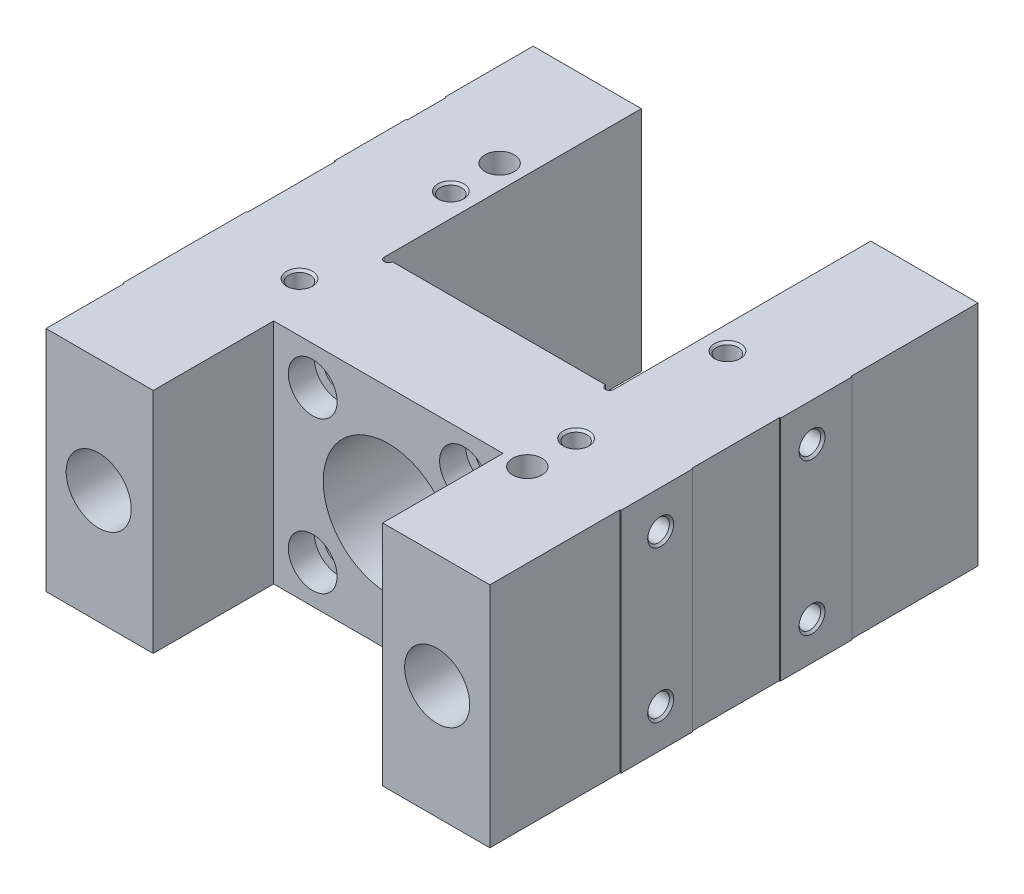
SolidWorks part; units mm, degrees
ref_plane "Front Plane" through (0, 0, 0) normal (0, 0, 1) x (1, 0, 0)
ref_plane "Top Plane" through (0, 0, 0) normal (0, 1, 0) x (1, 0, 0)
ref_plane "Right Plane" through (0, 0, 0) normal (1, 0, 0) x (0, 0, -1)
sketch "Sketch1" plane through (0, 0, 0) normal (0, 1, 0) x (1, 0, 0)
  line L0 (-68.5, -71) -> (-35.25, -71)
  line L1 (-35.25, -71) -> (-35.25, -34)
  line L2 (-35.25, -34) -> (35.25, -34)
  line L3 (35.25, -34) -> (35.25, -71)
  line L4 (35.25, -71) -> (68.5, -71)
  line L5 (68.5, -71) -> (68.5, 79)
  line L6 (68.5, 79) -> (35.25, 79)
  line L7 (35.25, 79) -> (35.25, 0)
  line L8 (32.75, 0) -> (-32.75, 0)
  line L9 (-35.25, 0) -> (-35.25, 79)
  line L10 (-35.25, 79) -> (-68.5, 79)
  line L11 (-68.5, 79) -> (-68.5, -71)
  arc A0 (35.25, 0) -> (32.75, 0) centre (34, 0) cw
  arc A1 (-32.75, 0) -> (-35.25, 0) centre (-34, 0) cw
extrude "Boss-Extrude1" add sketch "Sketch1" against normal blind 35 and the other way blind 35
sketch "Sketch2" plane through (0, 0, 0) normal (1, 0, 0) x (0, 0, -1)
  line L0 (-35, 0) -> (-35, 20)
  line L1 (-35, 20) -> (1, 20)
  line L2 (1, 20) -> (1, 0)
  line L3 (1, 0) -> (-35, 0)
  line L4 (1, 0) -> (-35, 0) construction
revolve "Cut-Revolve1" cut sketch "Sketch2" angle 360 about L4 reverse direction yes
ref_plane "Plane1" through (-23.25, 0, 0) normal (1, 0, 0) x (0, 0, -1)
sketch "Sketch3" plane through (-23.25, 0, 0) normal (1, 0, 0) x (0, 0, -1)
  line L0 (-34, 23.25) -> (-34, 30.75)
  line L1 (-34, 30.75) -> (-26, 30.75)
  line L2 (-26, 30.75) -> (-26, 27.75)
  line L3 (-26, 27.75) -> (0, 27.75)
  line L4 (0, 27.75) -> (0, 23.25)
  line L5 (0, 23.25) -> (-34, 23.25)
  line L6 (0, 23.25) -> (-34, 23.25) construction
revolve "Cut-Revolve2" cut sketch "Sketch3" angle 360 about L6 reverse direction yes
sketch "Sketch4" plane through (-23.25, 0, 0) normal (1, 0, 0) x (0, 0, -1)
  line L0 (-34, -23.25) -> (-34, -15.75)
  line L1 (-34, -15.75) -> (-26, -15.75)
  line L2 (-26, -15.75) -> (-26, -18.75)
  line L3 (-26, -18.75) -> (0, -18.75)
  line L4 (0, -18.75) -> (0, -23.25)
  line L5 (0, -23.25) -> (-34, -23.25)
  line L6 (0, -23.25) -> (-34, -23.25) construction
revolve "Cut-Revolve3" cut sketch "Sketch4" angle 360 about L6 reverse direction yes
ref_plane "Plane2" through (23.25, 0, 0) normal (1, 0, 0) x (0, 0, -1)
sketch "Sketch5" plane through (23.25, 0, 0) normal (1, 0, 0) x (0, 0, -1)
  line L0 (-34, 23.25) -> (-34, 30.75)
  line L1 (-34, 30.75) -> (-26, 30.75)
  line L2 (-26, 30.75) -> (-26, 27.75)
  line L3 (-26, 27.75) -> (0, 27.75)
  line L4 (0, 27.75) -> (0, 23.25)
  line L5 (0, 23.25) -> (-34, 23.25)
  line L6 (0, 23.25) -> (-34, 23.25) construction
revolve "Cut-Revolve4" cut sketch "Sketch5" angle 360 about L6 reverse direction yes
sketch "Sketch6" plane through (23.25, 0, 0) normal (1, 0, 0) x (0, 0, -1)
  line L0 (-34, -23.25) -> (-34, -15.75)
  line L1 (-34, -15.75) -> (-26, -15.75)
  line L2 (-26, -15.75) -> (-26, -18.75)
  line L3 (-26, -18.75) -> (0, -18.75)
  line L4 (0, -18.75) -> (0, -23.25)
  line L5 (0, -23.25) -> (-34, -23.25)
  line L6 (0, -23.25) -> (-34, -23.25) construction
revolve "Cut-Revolve5" cut sketch "Sketch6" angle 360 about L6 reverse direction yes
ref_plane "Plane3" through (0, 0, 18.8) normal (0, 0, 1) x (1, 0, 0)
hole_wizard "Hole1" positions "Sketch8" profile "Sketch7" legacy
sketch "Sketch8" plane through (0, 35, 0) normal (0, 1, 0) x (1, 0, 0)
  point P0 (42.5, -18.8)
sketch "Sketch7" plane through (42.5, 35, 18.8) normal (1, 0, 0) x (0, 0, 1)
  line L0 (0, 0) -> (0, 21.3333)
  line L1 (0, 21.3333) -> (3.3235, 19.4145)
  line L2 (3.3235, 19.4145) -> (3.3235, 0.6765)
  line L3 (3.3235, 0.6765) -> (4, 0)
  line L4 (4, 0) -> (0, 0)
  line L5 (0, -14.3089) -> (0, 102.4216) construction
  line L6 (0, 21.3333) -> (-3.3235, 19.4145) construction
  line L7 (-3.3235, 0.6765) -> (-4, 0) construction
  dimension "Diameter" = 6.647
  dimension "Depth" = 19.4145
  dimension "C-Sink Diameter" = 8
  dimension "C-Sink Angle" = 90
  dimension "Drill Angle" = 120
cosmetic thread "Cosmetic Thread1" parameters "D1"=16, "D2"=8
hole_wizard "Hole2" positions "Sketch10" profile "Sketch9" legacy
sketch "Sketch10" plane through (0, 35, 0) normal (0, 1, 0) x (1, 0, 0)
  point P0 (-42.5, -18.8)
sketch "Sketch9" plane through (-42.5, 35, 18.8) normal (1, 0, 0) x (0, 0, 1)
  line L0 (0, 0) -> (0, 21.3333)
  line L1 (0, 21.3333) -> (3.3235, 19.4145)
  line L2 (3.3235, 19.4145) -> (3.3235, 0.6765)
  line L3 (3.3235, 0.6765) -> (4, 0)
  line L4 (4, 0) -> (0, 0)
  line L5 (0, -14.3089) -> (0, 102.4216) construction
  line L6 (0, 21.3333) -> (-3.3235, 19.4145) construction
  line L7 (-3.3235, 0.6765) -> (-4, 0) construction
  dimension "Diameter" = 6.647
  dimension "Depth" = 19.4145
  dimension "C-Sink Diameter" = 8
  dimension "C-Sink Angle" = 90
  dimension "Drill Angle" = 120
cosmetic thread "Cosmetic Thread2" parameters "D1"=16, "D2"=8
sketch "Sketch11" plane through (0, 0, 18.8) normal (0, 0, 1) x (1, 0, 0)
  line L0 (48.5, 23.25) -> (50.4188, 26.5735)
  line L1 (50.4188, 26.5735) -> (67.8235, 26.5735)
  line L2 (67.8235, 26.5735) -> (68.5, 27.25)
  line L3 (68.5, 27.25) -> (68.5, 23.25)
  line L4 (68.5, 23.25) -> (48.5, 23.25)
  line L5 (68.5, 23.25) -> (48.5, 23.25) construction
revolve "Cut-Revolve6" cut sketch "Sketch11" angle 360 about L5
cosmetic thread "Cosmetic Thread3" parameters "D1"=16, "D2"=8
sketch "Sketch12" plane through (0, 0, 18.8) normal (0, 0, 1) x (1, 0, 0)
  line L0 (48.5, -23.25) -> (50.4188, -19.9265)
  line L1 (50.4188, -19.9265) -> (67.8235, -19.9265)
  line L2 (67.8235, -19.9265) -> (68.5, -19.25)
  line L3 (68.5, -19.25) -> (68.5, -23.25)
  line L4 (68.5, -23.25) -> (48.5, -23.25)
  line L5 (68.5, -23.25) -> (48.5, -23.25) construction
revolve "Cut-Revolve7" cut sketch "Sketch12" angle 360 about L5
cosmetic thread "Cosmetic Thread4" parameters "D1"=16, "D2"=8
sketch "Sketch13" plane through (0, 0, 18.8) normal (0, 0, 1) x (1, 0, 0)
  line L0 (-68.5, 23.25) -> (-68.5, 27.25)
  line L1 (-68.5, 27.25) -> (-67.8235, 26.5735)
  line L2 (-67.8235, 26.5735) -> (-50.4188, 26.5735)
  line L3 (-50.4188, 26.5735) -> (-48.5, 23.25)
  line L4 (-48.5, 23.25) -> (-68.5, 23.25)
  line L5 (-48.5, 23.25) -> (-68.5, 23.25) construction
revolve "Cut-Revolve8" cut sketch "Sketch13" angle 360 about L5
cosmetic thread "Cosmetic Thread5" parameters "D1"=16, "D2"=8
sketch "Sketch14" plane through (0, 0, 18.8) normal (0, 0, 1) x (1, 0, 0)
  line L0 (-68.5, -23.25) -> (-68.5, -19.25)
  line L1 (-68.5, -19.25) -> (-67.8235, -19.9265)
  line L2 (-67.8235, -19.9265) -> (-50.4188, -19.9265)
  line L3 (-50.4188, -19.9265) -> (-48.5, -23.25)
  line L4 (-48.5, -23.25) -> (-68.5, -23.25)
  line L5 (-48.5, -23.25) -> (-68.5, -23.25) construction
revolve "Cut-Revolve9" cut sketch "Sketch14" angle 360 about L5 reverse direction yes
cosmetic thread "Cosmetic Thread6" parameters "D1"=16, "D2"=8
ref_plane "Plane4" through (0, 0, -27.7) normal (0, 0, 1) x (1, 0, 0)
hole_wizard "Hole3" positions "Sketch16" profile "Sketch15" legacy
sketch "Sketch16" plane through (0, 35, 0) normal (0, 1, 0) x (1, 0, 0)
  point P0 (42.5, 27.7)
sketch "Sketch15" plane through (42.5, 35, -27.7) normal (1, 0, 0) x (0, 0, 1)
  line L0 (0, 0) -> (0, 21.3333)
  line L1 (0, 21.3333) -> (3.3235, 19.4145)
  line L2 (3.3235, 19.4145) -> (3.3235, 0.6765)
  line L3 (3.3235, 0.6765) -> (4, 0)
  line L4 (4, 0) -> (0, 0)
  line L5 (0, -14.3089) -> (0, 102.4216) construction
  line L6 (0, 21.3333) -> (-3.3235, 19.4145) construction
  line L7 (-3.3235, 0.6765) -> (-4, 0) construction
  dimension "Diameter" = 6.647
  dimension "Depth" = 19.4145
  dimension "C-Sink Diameter" = 8
  dimension "C-Sink Angle" = 90
  dimension "Drill Angle" = 120
cosmetic thread "Cosmetic Thread7" parameters "D1"=16, "D2"=8
sketch "Sketch17" plane through (0, 0, -27.7) normal (0, 0, 1) x (1, 0, 0)
  line L0 (-42.5, 35) -> (-38.5, 35)
  line L1 (-38.5, 35) -> (-39.1765, 34.3235)
  line L2 (-39.1765, 34.3235) -> (-39.1765, 15.5855)
  line L3 (-39.1765, 15.5855) -> (-42.5, 13.6667)
  line L4 (-42.5, 13.6667) -> (-42.5, 35)
  line L5 (-42.5, 13.6667) -> (-42.5, 35) construction
revolve "Cut-Revolve10" cut sketch "Sketch17" angle 360 about L5
cosmetic thread "Cosmetic Thread8" parameters "D1"=16, "D2"=8
sketch "Sketch18" plane through (0, 0, -27.7) normal (0, 0, 1) x (1, 0, 0)
  line L0 (48.5, 23.25) -> (50.4188, 26.5735)
  line L1 (50.4188, 26.5735) -> (67.8235, 26.5735)
  line L2 (67.8235, 26.5735) -> (68.5, 27.25)
  line L3 (68.5, 27.25) -> (68.5, 23.25)
  line L4 (68.5, 23.25) -> (48.5, 23.25)
  line L5 (68.5, 23.25) -> (48.5, 23.25) construction
revolve "Cut-Revolve11" cut sketch "Sketch18" angle 360 about L5
cosmetic thread "Cosmetic Thread9" parameters "D1"=16, "D2"=8
sketch "Sketch19" plane through (0, 0, -27.7) normal (0, 0, 1) x (1, 0, 0)
  line L0 (48.5, -23.25) -> (50.4188, -19.9265)
  line L1 (50.4188, -19.9265) -> (67.8235, -19.9265)
  line L2 (67.8235, -19.9265) -> (68.5, -19.25)
  line L3 (68.5, -19.25) -> (68.5, -23.25)
  line L4 (68.5, -23.25) -> (48.5, -23.25)
  line L5 (68.5, -23.25) -> (48.5, -23.25) construction
revolve "Cut-Revolve12" cut sketch "Sketch19" angle 360 about L5
cosmetic thread "Cosmetic Thread10" parameters "D1"=16, "D2"=8
sketch "Sketch20" plane through (0, 0, -27.7) normal (0, 0, 1) x (1, 0, 0)
  line L0 (-68.5, 23.25) -> (-68.5, 27.25)
  line L1 (-68.5, 27.25) -> (-67.8235, 26.5735)
  line L2 (-67.8235, 26.5735) -> (-50.4188, 26.5735)
  line L3 (-50.4188, 26.5735) -> (-48.5, 23.25)
  line L4 (-48.5, 23.25) -> (-68.5, 23.25)
  line L5 (-48.5, 23.25) -> (-68.5, 23.25) construction
revolve "Cut-Revolve13" cut sketch "Sketch20" angle 360 about L5
cosmetic thread "Cosmetic Thread11" parameters "D1"=16, "D2"=8
sketch "Sketch21" plane through (0, 0, -27.7) normal (0, 0, 1) x (1, 0, 0)
  line L0 (-68.5, -23.25) -> (-68.5, -19.25)
  line L1 (-68.5, -19.25) -> (-67.8235, -19.9265)
  line L2 (-67.8235, -19.9265) -> (-50.4188, -19.9265)
  line L3 (-50.4188, -19.9265) -> (-48.5, -23.25)
  line L4 (-48.5, -23.25) -> (-68.5, -23.25)
  line L5 (-48.5, -23.25) -> (-68.5, -23.25) construction
revolve "Cut-Revolve14" cut sketch "Sketch21" angle 360 about L5
cosmetic thread "Cosmetic Thread12" parameters "D1"=16, "D2"=8
ref_plane "Plane5" through (0, 0, -63) normal (0, 0, 1) x (1, 0, 0)
sketch "Sketch22" plane through (0, 0, -63) normal (0, 0, 1) x (1, 0, 0)
  line L0 (-68.5, 23.25) -> (-68.5, 27.25)
  line L1 (-68.5, 27.25) -> (-67.8235, 26.5735)
  line L2 (-67.8235, 26.5735) -> (-50.4188, 26.5735)
  line L3 (-50.4188, 26.5735) -> (-48.5, 23.25)
  line L4 (-48.5, 23.25) -> (-68.5, 23.25)
  line L5 (-48.5, 23.25) -> (-68.5, 23.25) construction
revolve "Cut-Revolve15" cut sketch "Sketch22" angle 360 about L5
cosmetic thread "Cosmetic Thread13" parameters "D1"=16, "D2"=8
sketch "Sketch23" plane through (0, 0, -63) normal (0, 0, 1) x (1, 0, 0)
  line L0 (-68.5, -23.25) -> (-68.5, -19.25)
  line L1 (-68.5, -19.25) -> (-67.8235, -19.9265)
  line L2 (-67.8235, -19.9265) -> (-50.4188, -19.9265)
  line L3 (-50.4188, -19.9265) -> (-48.5, -23.25)
  line L4 (-48.5, -23.25) -> (-68.5, -23.25)
  line L5 (-48.5, -23.25) -> (-68.5, -23.25) construction
revolve "Cut-Revolve16" cut sketch "Sketch23" angle 360 about L5
cosmetic thread "Cosmetic Thread14" parameters "D1"=16, "D2"=8
ref_plane "Plane6" through (0, 0, 37) normal (0, 0, 1) x (1, 0, 0)
sketch "Sketch24" plane through (0, 0, 37) normal (0, 0, 1) x (1, 0, 0)
  line L0 (-68.5, 23.25) -> (-68.5, 27.25)
  line L1 (-68.5, 27.25) -> (-67.8235, 26.5735)
  line L2 (-67.8235, 26.5735) -> (-50.4188, 26.5735)
  line L3 (-50.4188, 26.5735) -> (-48.5, 23.25)
  line L4 (-48.5, 23.25) -> (-68.5, 23.25)
  line L5 (-48.5, 23.25) -> (-68.5, 23.25) construction
revolve "Cut-Revolve17" cut sketch "Sketch24" angle 360 about L5
cosmetic thread "Cosmetic Thread15" parameters "D1"=16, "D2"=8
sketch "Sketch25" plane through (0, 0, 37) normal (0, 0, 1) x (1, 0, 0)
  line L0 (-68.5, -23.25) -> (-68.5, -19.25)
  line L1 (-68.5, -19.25) -> (-67.8235, -19.9265)
  line L2 (-67.8235, -19.9265) -> (-50.4188, -19.9265)
  line L3 (-50.4188, -19.9265) -> (-48.5, -23.25)
  line L4 (-48.5, -23.25) -> (-68.5, -23.25)
  line L5 (-48.5, -23.25) -> (-68.5, -23.25) construction
revolve "Cut-Revolve18" cut sketch "Sketch25" angle 360 about L5
cosmetic thread "Cosmetic Thread16" parameters "D1"=16, "D2"=8
ref_plane "Plane7" through (0, 0, -79) normal (0, 0, 1) x (1, 0, 0)
sketch "Sketch26" plane through (0, 0, -79) normal (0, 0, 1) x (1, 0, 0)
  circle A0 centre (52, 0) radius 10
extrude "Cut-Extrude1" cut sketch "Sketch26" along normal blind 150
sketch "Sketch27" plane through (0, 0, -79) normal (0, 0, 1) x (1, 0, 0)
  circle A0 centre (-52, 0) radius 10
extrude "Cut-Extrude2" cut sketch "Sketch27" along normal blind 150
ref_plane "Plane8" through (0, 0, 26) normal (0, 0, 1) x (1, 0, 0)
ref_plane "Plane9" through (0, 0, 0) normal (0, 0, 1) x (1, 0, 0)
sketch "Sketch28" plane through (0, 0, 0) normal (0, 1, 0) x (1, 0, 0)
  line L0 (-88.5, -91) -> (88.5, -91)
  line L1 (88.5, -91) -> (88.5, 99)
  line L2 (88.5, 99) -> (-88.5, 99)
  line L3 (-88.5, 99) -> (-88.5, -91)
  line L4 (-68.5, 18) -> (-68.2, 18)
  line L5 (-68.2, 18) -> (-68.2, -9)
  line L6 (-68.2, -9) -> (-68.5, -9)
  line L7 (-68.5, -9) -> (-68.5, -47)
  line L8 (-68.5, -47) -> (-68.2, -47)
  line L9 (-68.2, -47) -> (-68.2, -71)
  line L10 (-68.2, -71) -> (68.2, -71)
  line L11 (68.2, -71) -> (68.2, -31)
  line L12 (68.2, -31) -> (68.5, -31)
  line L13 (68.5, -31) -> (68.5, -9)
  line L14 (68.5, -9) -> (68.2, -9)
  line L15 (68.2, -9) -> (68.2, 18)
  line L16 (68.2, 18) -> (68.5, 18)
  line L17 (68.5, 18) -> (68.5, 40)
  line L18 (68.5, 40) -> (68.2, 40)
  line L19 (68.2, 40) -> (68.2, 79)
  line L20 (68.2, 79) -> (-68.5, 79)
  line L21 (-68.5, 79) -> (-68.5, 52)
  line L22 (-68.5, 52) -> (-68.2, 52)
  line L23 (-68.2, 52) -> (-68.2, 40)
  line L24 (-68.2, 40) -> (-68.5, 40)
  line L25 (-68.5, 40) -> (-68.5, 18)
extrude "Cut-Extrude3" cut sketch "Sketch28" along normal blind 70 and the other way blind 70
ref_plane "Plane10" through (0, 0, 18.8) normal (0, 0, 1) x (1, 0, 0)
ref_plane "Plane11" through (-68.2, 0, 0) normal (1, 0, 0) x (0, 0, -1)
ref_plane "Plane12" through (0, 35, 0) normal (0, 1, 0) x (1, 0, 0)
ref_plane "DIN912 1 XY" through (0, 0, 26) normal (0, 0, 1) x (1, 0, 0)
ref_plane "DIN912 1 XZ" through (0, 23.25, 0) normal (0, -1, 0) x (-1, 0, 0)
ref_plane "DIN912 1 YZ" through (23.25, 0, 0) normal (1, 0, 0) x (0, 0, -1)
ref_axis "DIN912 1 X" through (-80.9, 23.25, 26) along (1, 0, 0)
ref_axis "DIN912 1 Y" through (23.25, -50, 26) along (0, 1, 0)
ref_axis "DIN912 1 Z" through (23.25, 23.25, 80.9) along (0, 0, -1)
sketch3d "DIN912 1"
  point P0 (23.25, 23.25, 26)
ref_plane "DIN912 2 XY" through (0, 0, 26) normal (0, 0, 1) x (1, 0, 0)
ref_plane "DIN912 2 XZ" through (0, 23.25, 0) normal (0, -1, 0) x (-1, 0, 0)
ref_plane "DIN912 2 YZ" through (-23.25, 0, 0) normal (1, 0, 0) x (0, 0, -1)
ref_axis "DIN912 2 X" through (-80.9, 23.25, 26) along (1, 0, 0)
ref_axis "DIN912 2 Y" through (-23.25, -50, 26) along (0, 1, 0)
ref_axis "DIN912 2 Z" through (-23.25, 23.25, 80.9) along (0, 0, -1)
sketch3d "DIN912 2"
  point P0 (-23.25, 23.25, 26)
ref_plane "DIN912 3 XY" through (0, 0, 26) normal (0, 0, 1) x (1, 0, 0)
ref_plane "DIN912 3 XZ" through (0, -23.25, 0) normal (0, -1, 0) x (-1, 0, 0)
ref_plane "DIN912 3 YZ" through (23.25, 0, 0) normal (1, 0, 0) x (0, 0, -1)
ref_axis "DIN912 3 X" through (-80.9, -23.25, 26) along (1, 0, 0)
ref_axis "DIN912 3 Y" through (23.25, -50, 26) along (0, 1, 0)
ref_axis "DIN912 3 Z" through (23.25, -23.25, 80.9) along (0, 0, -1)
sketch3d "DIN912 3"
  point P0 (23.25, -23.25, 26)
ref_plane "DIN912 4 XY" through (0, 0, 26) normal (0, 0, 1) x (1, 0, 0)
ref_plane "DIN912 4 XZ" through (0, -23.25, 0) normal (0, -1, 0) x (-1, 0, 0)
ref_plane "DIN912 4 YZ" through (-23.25, 0, 0) normal (1, 0, 0) x (0, 0, -1)
ref_axis "DIN912 4 X" through (-80.9, -23.25, 26) along (1, 0, 0)
ref_axis "DIN912 4 Y" through (-23.25, -50, 26) along (0, 1, 0)
ref_axis "DIN912 4 Z" through (-23.25, -23.25, 80.9) along (0, 0, -1)
sketch3d "DIN912 4"
  point P0 (-23.25, -23.25, 26)
ref_plane "JOCH XY" through (0, 0, 0) normal (0, 0, 1) x (1, 0, 0)
ref_plane "JOCH XZ" through (0, 0, 0) normal (0, -1, 0) x (-1, 0, 0)
ref_plane "JOCH YZ" through (0, 0, 0) normal (1, 0, 0) x (0, 0, -1)
ref_axis "JOCH X" through (-80.9, 0, 0) along (1, 0, 0)
ref_axis "JOCH Y" through (0, -50, 0) along (0, 1, 0)
ref_axis "JOCH Z" through (0, 0, 80.9) along (0, 0, -1)
sketch3d "JOCH"
  point P0 (0, 0, 0)
ref_plane "SCHRAUBE1 XY" through (0, 0, 26) normal (0, 0, 1) x (1, 0, 0)
ref_plane "SCHRAUBE1 XZ" through (0, 23.25, 0) normal (0, -1, 0) x (-1, 0, 0)
ref_plane "SCHRAUBE1 YZ" through (23.25, 0, 0) normal (1, 0, 0) x (0, 0, -1)
ref_axis "SCHRAUBE1 X" through (-80.9, 23.25, 26) along (1, 0, 0)
ref_axis "SCHRAUBE1 Y" through (23.25, -50, 26) along (0, 1, 0)
ref_axis "SCHRAUBE1 Z" through (23.25, 23.25, 80.9) along (0, 0, -1)
sketch3d "SCHRAUBE1"
  point P0 (23.25, 23.25, 26)
ref_plane "SCHRAUBE2 XY" through (0, 0, 26) normal (0, 0, 1) x (1, 0, 0)
ref_plane "SCHRAUBE2 XZ" through (0, 23.25, 0) normal (0, -1, 0) x (-1, 0, 0)
ref_plane "SCHRAUBE2 YZ" through (-23.25, 0, 0) normal (1, 0, 0) x (0, 0, -1)
ref_axis "SCHRAUBE2 X" through (-80.9, 23.25, 26) along (1, 0, 0)
ref_axis "SCHRAUBE2 Y" through (-23.25, -50, 26) along (0, 1, 0)
ref_axis "SCHRAUBE2 Z" through (-23.25, 23.25, 80.9) along (0, 0, -1)
sketch3d "SCHRAUBE2"
  point P0 (-23.25, 23.25, 26)
ref_plane "SCHRAUBE3 XY" through (0, 0, 26) normal (0, 0, 1) x (1, 0, 0)
ref_plane "SCHRAUBE3 XZ" through (0, -23.25, 0) normal (0, -1, 0) x (-1, 0, 0)
ref_plane "SCHRAUBE3 YZ" through (-23.25, 0, 0) normal (1, 0, 0) x (0, 0, -1)
ref_axis "SCHRAUBE3 X" through (-80.9, -23.25, 26) along (1, 0, 0)
ref_axis "SCHRAUBE3 Y" through (-23.25, -50, 26) along (0, 1, 0)
ref_axis "SCHRAUBE3 Z" through (-23.25, -23.25, 80.9) along (0, 0, -1)
sketch3d "SCHRAUBE3"
  point P0 (-23.25, -23.25, 26)
ref_plane "SCHRAUBE4 XY" through (0, 0, 26) normal (0, 0, 1) x (1, 0, 0)
ref_plane "SCHRAUBE4 XZ" through (0, -23.25, 0) normal (0, -1, 0) x (-1, 0, 0)
ref_plane "SCHRAUBE4 YZ" through (23.25, 0, 0) normal (1, 0, 0) x (0, 0, -1)
ref_axis "SCHRAUBE4 X" through (-80.9, -23.25, 26) along (1, 0, 0)
ref_axis "SCHRAUBE4 Y" through (23.25, -50, 26) along (0, 1, 0)
ref_axis "SCHRAUBE4 Z" through (23.25, -23.25, 80.9) along (0, 0, -1)
sketch3d "SCHRAUBE4"
  point P0 (23.25, -23.25, 26)
ref_plane "ZYLINDER XY" through (0, 0, 0) normal (0, 0, 1) x (1, 0, 0)
ref_plane "ZYLINDER XZ" through (0, 0, 0) normal (0, -1, 0) x (-1, 0, 0)
ref_plane "ZYLINDER YZ" through (0, 0, 0) normal (1, 0, 0) x (0, 0, -1)
ref_axis "ZYLINDER X" through (-80.9, 0, 0) along (1, 0, 0)
ref_axis "ZYLINDER Y" through (0, -50, 0) along (0, 1, 0)
ref_axis "ZYLINDER Z" through (0, 0, 80.9) along (0, 0, -1)
sketch3d "ZYLINDER"
  point P0 (0, 0, 0)
other "Freeze***"
sketch "Sketch29" plane through (0, 35, 0) normal (0, 1, 0) x (1, 0, 0)
  circle A0 centre (-42.5, 42.7) radius 4.5
  circle A1 centre (42.5, -33.8) radius 4.5
  dimension "D1" = 9
  dimension "D2" = 15
  dimension "D3" = 15
extrude "Cut-Extrude4" cut sketch "Sketch29" against normal blind 17.5
